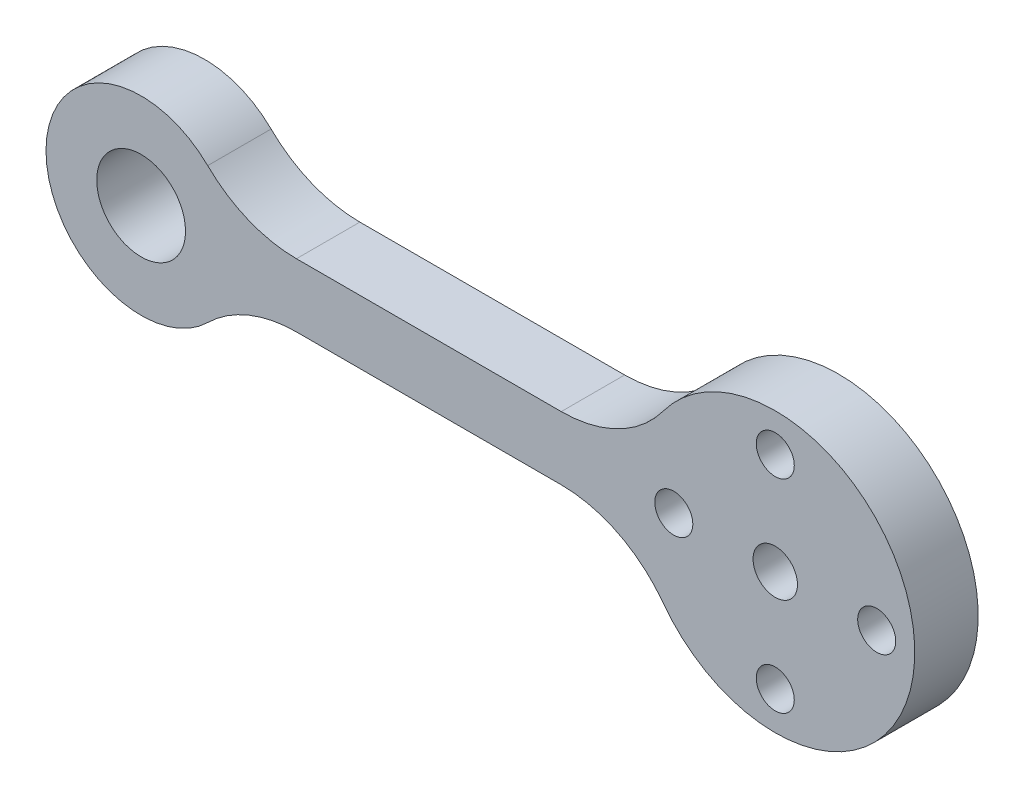
SolidWorks part; units mm, degrees
note: The reader was unsure of these and kept them because the rebuilt part matched: thickness of "Base-Flange1", "Sheet-Metal1".
ref_plane "Front Plane" through (0, 0, 0) normal (0, 0, 1) x (1, 0, 0)
ref_plane "Top Plane" through (0, 0, 0) normal (0, 1, 0) x (1, 0, 0)
ref_plane "Right Plane" through (0, 0, 0) normal (1, 0, 0) x (0, 0, -1)
sketch "Sketch1" plane through (0, 0, 0) normal (0, 0, 1) x (1, 0, 0)
  line L0 (42, 0) -> (58, 0) construction
  line L1 (7.0711, 2.5) -> (39.2879, 2.5)
  line L2 (7.0711, 2.5) -> (7.0711, -2.5) construction
  line L3 (7.0711, -2.5) -> (39.2879, -2.5)
  line L4 (39.2879, 2.5) -> (39.2879, -2.5) construction
  line L5 (50, 8) -> (50, -8) construction
  circle A0 centre (0, 0) radius 3.5
  arc A1 (7.0711, 2.5) -> (7.0711, -2.5) centre (0, 0) ccw
  arc A2 (39.2879, -2.5) -> (39.2879, 2.5) centre (50, 0) ccw
  circle A3 centre (50, 8) radius 1.5
  circle A4 centre (58, 0) radius 1.5
  circle A5 centre (50, -8) radius 1.5
  circle A6 centre (42, 0) radius 1.5
  arc A7 (39.2879, 2.5) -> (39.2879, -2.5) centre (50, 0) ccw construction
  arc A8 (7.0711, -2.5) -> (7.0711, 2.5) centre (0, 0) ccw construction
  circle A9 centre (50, 0) radius 1.75
  point P18 (50, 0)
  point P19 (50, 0)
  dimension "D1" = 7
  dimension "D2" = 15
  dimension "D3" = 22
  dimension "D6" = 3
  dimension "D8" = 3.5
  dimension "D4" = 5
  dimension "D5" = 50
  dimension "D7" = 16
base flange "Base-Flange1" sketch "Sketch1" thickness 5 reverse thickness direction no parameters "D1"=0.7366
fillet "Fillet1" radius 10 4 edges at (39.2879, -2.5, -2.5) (39.2879, 2.5, -2.5) (7.0711, -2.5, -2.5) (7.0711, 2.5, -2.5)
sketch "Bend-Lines1" [suppressed] plane through (0, 0, 0) normal (0, 1, 0) x (1, 0, 0)
sketch "Bounding-Box1" [suppressed] plane through (0, 0, 0) normal (0, 1, 0) x (1, 0, 0)
sheet metal parameters "Sheet-Metal1" thickness 5 parameters "D1"=0.7366
flat pattern "Flat-Pattern1" [suppressed]
sketch "Bend-Lines2" plane through (0, 0, 0) normal (0, 1, 0) x (1, 0, 0)
sketch3d "Bounding-Box2" [suppressed]
  line L0 (-6.4665, -14.9895, 0) -> (61.743, -10.2029, 0) construction
  line L1 (-8.0066, 6.9565, 0) -> (60.203, 11.743, 0) construction
  line L2 (-6.4665, -14.9895, 0) -> (-8.0066, 6.9565, 0) construction
  line L3 (61.743, -10.2029, 0) -> (60.203, 11.743, 0) construction
